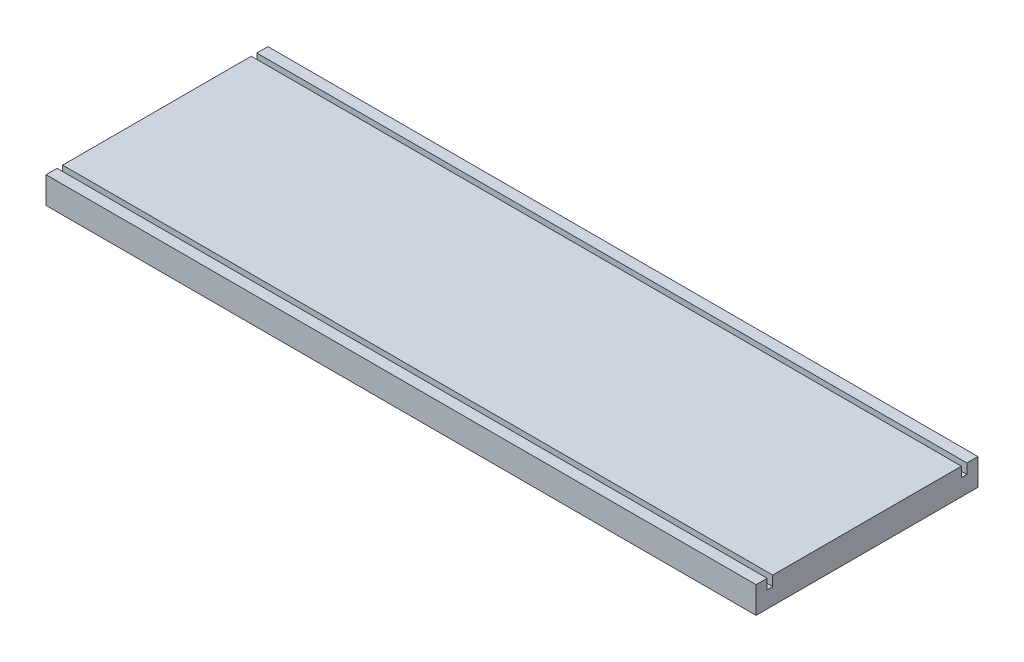
SolidWorks part; units mm, degrees
ref_plane "Front Plane" through (0, 0, 0) normal (0, 0, 1) x (1, 0, 0)
ref_plane "Top Plane" through (0, 0, 0) normal (0, 1, 0) x (1, 0, 0)
ref_plane "Right Plane" through (0, 0, 0) normal (1, 0, 0) x (0, 0, -1)
sketch "Sketch1" plane through (0, 0, 0) normal (0, 1, 0) x (1, 0, 0)
  line L1 (80, -25) -> (-80, -25)
  line L2 (80, -25) -> (80, 25)
  line L3 (80, 25) -> (-80, 25)
  line L4 (-80, -25) -> (-80, 25)
  line L5 (80, -25) -> (-80, 25) construction
  line L6 (80, 25) -> (-80, -25) construction
  point P0 (0, 0)
  dimension "D1" = 50
  dimension "D2" = 160
extrude "Boss-Extrude1" add sketch "Sketch1" along normal blind 6
sketch "Sketch3" plane through (0, 6, 0) normal (0, 1, 0) x (1, 0, 0)
  line L0 (-80, 25) -> (-80, -25) construction
  line L1 (-80, -22.5) -> (80, -22.5)
  line L2 (-80, -22.5) -> (-80, -21.25)
  line L3 (-80, -21.25) -> (80, -21.25)
  line L4 (80, -22.5) -> (80, -21.25)
  line L5 (80, -25) -> (80, 25) construction
  line L6 (-80, -25) -> (80, -25) construction
  dimension "D1" = 1.25
  dimension "D2" = 2.5
extrude "Cut-Extrude1" cut sketch "Sketch3" against normal blind 2.25
ref_axis "Axis1" through (-88, 0, 0) along (1, 0, 0)
ref_plane "Plane2" through (0, 0, 0) normal (0, 0, 1) x (1, 0, 0)
mirror "Mirror1" about plane through (0, 0, 0) normal (0, 0, 1) of "Cut-Extrude1"
